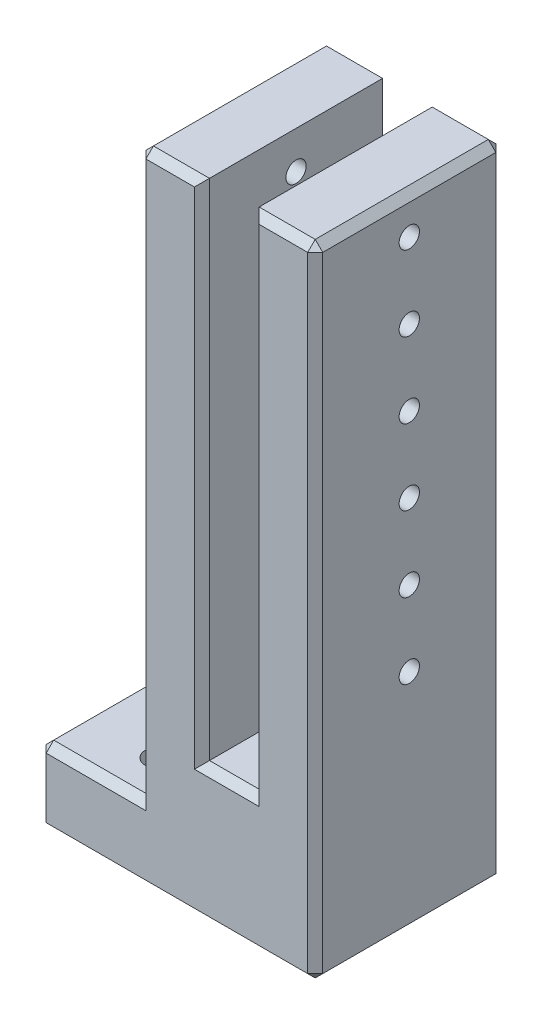
SolidWorks part; units mm, degrees
material "PBT General Purpose"
ref_plane "Front Plane" through (0, 0, 0) normal (0, 0, 1) x (1, 0, 0)
ref_plane "Top Plane" through (0, 0, 0) normal (0, 1, 0) x (1, 0, 0)
ref_plane "Right Plane" through (0, 0, 0) normal (1, 0, 0) x (0, 0, -1)
sketch "Sketch1" plane through (0, 0, 0) normal (0, 1, 0) x (1, 0, 0)
  line L1 (0, 0) -> (50, 0)
  line L2 (0, 0) -> (0, 25)
  line L3 (0, 25) -> (50, 25)
  line L4 (50, 0) -> (50, 25)
  dimension "D1" = 50
  dimension "D2" = 25
extrude "Boss-Extrude1" add sketch "Sketch1" along normal blind 10
sketch "Sketch2" plane through (0, 10, 0) normal (0, 1, 0) x (1, 0, 0)
  line L0 (50, 25) -> (0, 25) construction
  line L1 (15, 25) -> (35, 25)
  line L2 (15, 25) -> (15, 0)
  line L3 (15, 0) -> (35, 0)
  line L4 (35, 25) -> (35, 0)
  line L5 (0, 0) -> (50, 0) construction
  point P8 (25, 25)
  point P9 (25, 25)
  dimension "D1" = 20
extrude "Boss-Extrude2" add sketch "Sketch2" along normal blind 75
sketch "Sketch3" plane through (0, 85, 0) normal (0, 1, 0) x (1, 0, 0)
  line L0 (35, 25) -> (15, 25) construction
  line L1 (21.7, 25) -> (28.3, 25)
  line L2 (21.7, 25) -> (21.7, 0)
  line L3 (21.7, 0) -> (28.3, 0)
  line L4 (28.3, 25) -> (28.3, 0)
  line L5 (15, 0) -> (35, 0) construction
  point P8 (25, 25)
  point P9 (25, 25)
  dimension "D1" = 6.6
extrude "Cut-Extrude1" cut sketch "Sketch3" against normal up to surface (75 mm away) up to face at (7.5, 10, -12.5)
sketch "Sketch4" plane through (15, 0, 0) normal (-1, 0, 0) x (0, 0, 1)
  line L0 (-12.5, 85) -> (-12.5, 80) construction
  line L1 (-25, 85) -> (0, 85) construction
  circle A0 centre (-12.5, 80) radius 1.35
  dimension "D1" = 5
  dimension "D2" = 2.7
extrude "Cut-Extrude2" cut sketch "Sketch4" against normal through all and the other way through all
pattern_linear "LPattern1" count 6 spacing 10 along (0, -1, 0) of "Cut-Extrude2"
sketch "Sketch5" plane through (0, 10, 0) normal (0, 1, 0) x (1, 0, 0)
  line L4 (35, 25) -> (35, 0)
  line L5 (35, 0) -> (50, 0)
  line L6 (50, 0) -> (50, 25)
  line L7 (50, 25) -> (35, 25)
  line L8 (35, 25) -> (35, 0)
  line L9 (35, 0) -> (50, 0)
  line L10 (50, 0) -> (50, 25)
  line L11 (50, 25) -> (35, 25)
  dimension "D1" = 0
extrude "Cut-Extrude3" cut sketch "Sketch5" against normal through all
ref_plane "Plane1" through (25, 0, 0) normal (1, 0, 0) x (0, 0, -1)
sketch "Sketch6" plane through (0, 0, 0) normal (0, -1, 0) x (1, 0, 0)
  line L0 (0, 0) -> (35, 0) construction
  line L1 (0, -25) -> (0, 0) construction
  circle A1 centre (10.0004, -5.9306) radius 1.75
  dimension "D1" = 5.9306
  dimension "D2" = 10.0004
  dimension "D3" = 3.5
extrude "Cut-Extrude4" cut sketch "Sketch6" against normal through all
ref_plane "Plane2" through (0, 0, -12.5) normal (0, 0, 1) x (1, 0, 0)
mirror "Mirror1" about plane through (0, 0, -12.5) normal (0, 0, 1) of "Cut-Extrude4"
sketch "Sketch7" plane through (0, 10, 0) normal (0, 1, 0) x (1, 0, 0)
  line L0 (0, 0) -> (35, 0) construction
  circle A1 centre (10.0004, 14.5906) radius 1.75
  circle A3 centre (10.0004, 5.9306) radius 1.75 construction
  circle A4 centre (10.0004, 5.9306) radius 1.75
  point P7 (0, 0)
  dimension "D1" = 14.5906
extrude "Cut-Extrude5" cut sketch "Sketch7" against normal through all
sketch "Sketch8" plane through (0, 0, 0) normal (0, 0, 1) x (1, 0, 0)
  line L0 (28.3, 10) -> (28.3, 85) construction
  line L1 (21.7, 10) -> (28.3, 10)
  line L2 (21.7, 10) -> (21.7, 18)
  line L3 (21.7, 18) -> (28.3, 18)
  line L4 (28.3, 10) -> (28.3, 18)
  dimension "D1" = 8
extrude "Boss-Extrude4" add sketch "Sketch8" against normal through all
sketch "Sketch11" plane through (35, 0, 0) normal (1, 0, 0) x (0, 0, -1)
  line L8 (0, 85) -> (0, 0)
  line L9 (0, 0) -> (25, 0)
  line L10 (25, 0) -> (25, 85)
  line L11 (25, 85) -> (0, 85)
  line L12 (0, 85) -> (0, 0)
  line L13 (0, 0) -> (25, 0)
  line L14 (25, 0) -> (25, 85)
  line L15 (25, 85) -> (0, 85)
  dimension "D1" = 0
extrude "Boss-Extrude5" add sketch "Sketch11" along normal blind 1.75
sketch "Sketch12" plane through (15, 0, 0) normal (-1, 0, 0) x (0, 0, 1)
  line L4 (-25, 10) -> (0, 10)
  line L5 (0, 10) -> (0, 85)
  line L6 (0, 85) -> (-25, 85)
  line L7 (-25, 85) -> (-25, 10)
  line L8 (-25, 10) -> (0, 10)
  line L9 (0, 10) -> (0, 85)
  line L10 (0, 85) -> (-25, 85)
  line L11 (-25, 85) -> (-25, 10)
  dimension "D1" = 0
extrude "Boss-Extrude6" add sketch "Sketch12" along normal blind 1.75
sketch "Sketch14" plane through (0, 10, 0) normal (0, 1, 0) x (1, 0, 0)
  line L0 (10.0004, 14.5906) -> (10.0004, 5.9306) construction
  circle A0 centre (10.0004, 10.2606) radius 1.75
  circle A1 centre (10.0004, 5.9306) radius 1.75 construction
extrude "Cut-Extrude7" cut sketch "Sketch14" against normal through all
sketch "Sketch15" plane through (28.3, 0, 0) normal (-1, 0, 0) x (0, 0, 1)
  circle A0 centre (-12.5, 30) radius 1.35 construction
  circle A1 centre (-12.5, 40) radius 1.35 construction
  circle A2 centre (-12.5, 50) radius 1.35 construction
  circle A3 centre (-12.5, 60) radius 1.35 construction
  circle A4 centre (-12.5, 70) radius 1.35 construction
  circle A5 centre (-12.5, 80) radius 1.35 construction
  circle A6 centre (-12.5, 30) radius 1.35
  circle A7 centre (-12.5, 40) radius 1.35
  circle A8 centre (-12.5, 50) radius 1.35
  circle A9 centre (-12.5, 60) radius 1.35
  circle A10 centre (-12.5, 70) radius 1.35
  circle A11 centre (-12.5, 80) radius 1.35
extrude "Cut-Extrude8" cut sketch "Sketch15" against normal through all and the other way through all
chamfer "Chamfer1" distance 1 angle 45 25 edges at (36.75, 0, -12.5) (36.75, 85, -12.5) (32.525, 85, 0) (36.75, 42.5, 0) (18.375, 0, 0) (0, 5, 0) (6.625, 10, 0) (13.25, 47.5, 0) (28.3, 51.5, 0) (25, 18, 0) (21.7, 51.5, 0) (17.475, 85, 0) (0, 5, -25) (0, 0, -12.5) (18.375, 0, -25) (36.75, 42.5, -25) (32.525, 85, -25) (28.3, 51.5, -25) (25, 18, -25) (21.7, 51.5, -25) (17.475, 85, -25) (13.25, 85, -12.5) (13.25, 47.5, -25) (6.625, 10, -25) (0, 10, -12.5)
